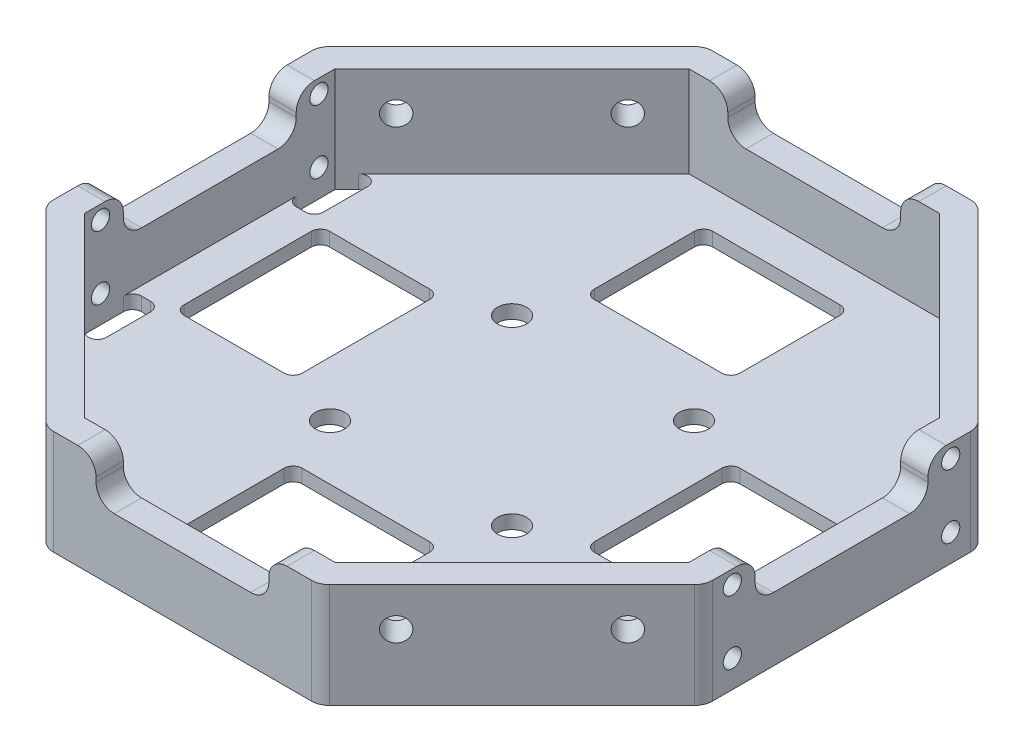
SolidWorks part; units mm, degrees
ref_plane "Front Plane" through (0, 0, 0) normal (0, 0, 1) x (1, 0, 0)
ref_plane "Top Plane" through (0, 0, 0) normal (0, 1, 0) x (1, 0, 0)
ref_plane "Right Plane" through (0, 0, 0) normal (1, 0, 0) x (0, 0, -1)
sketch "Sketch1" plane through (0, 0, 0) normal (0, 1, 0) x (1, 0, 0)
  line L1 (-11.2132, 40) -> (18.7868, 40)
  line L2 (18.7868, 40) -> (40, 18.7868)
  line L3 (40, 18.7868) -> (40, -11.2132)
  line L5 (-32.4264, 18.7868) -> (-32.4264, -11.2132)
  line L6 (-11.2132, 40) -> (-32.4264, 18.7868)
  line L7 (18.7868, -32.4264) -> (40, -11.2132)
  line L8 (-11.2132, -32.4264) -> (18.7868, -32.4264)
  line L9 (-11.2132, -32.4264) -> (-32.4264, -11.2132)
  point P13 (-32.4264, 3.7868)
  dimension "D1" = 30
  dimension "D2" = 30
  dimension "D3" = 40
  dimension "D4" = 40
extrude "Boss-Extrude1" add sketch "Sketch1" along normal blind 11.5
shell "Shell1" thickness 3 removed face at (3.7868, 11.5, -3.7868)
sketch "Sketch3" plane through (-21.8198, 0, 21.8198) normal (-0.7071, 0, 0.7071) x (0.7071, 0, 0.7071)
  line L0 (0, 11.5) -> (0, 7.25) construction
  line L1 (-15, 11.5) -> (15, 11.5) construction
  line L2 (0, 7.25) -> (9, 7.25) construction
  line L3 (0, 7.25) -> (-9, 7.25) construction
  circle A0 centre (-9, 7.25) radius 1.3
  circle A1 centre (9, 7.25) radius 1.3
extrude "Cut-Extrude1" cut sketch "Sketch3" against normal blind 94
sketch "Sketch4" plane through (-25.6066, 0, -25.6066) normal (-0.7071, 0, -0.7071) x (-0.7071, 0, 0.7071)
  line L0 (-5.3553, 11.5) -> (-5.3553, 7.25) construction
  line L1 (-20.3553, 11.5) -> (9.6447, 11.5) construction
  line L2 (-5.3553, 7.25) -> (-14.3553, 7.25) construction
  line L3 (-5.3553, 7.25) -> (3.6447, 7.25) construction
  circle A0 centre (-14.3553, 7.25) radius 1.3
  circle A1 centre (3.6447, 7.25) radius 1.3
extrude "Cut-Extrude2" cut sketch "Sketch4" against normal blind 94
fillet "Fillet1" radius 2 8 edges at (40, 5.75, 11.2132) (18.7868, 5.75, 32.4264) (40, 5.75, -18.7868) (18.7868, 5.75, -40) (-11.2132, 5.75, -40) (-32.4264, 5.75, -18.7868) (-32.4264, 5.75, 11.2132) (-11.2132, 5.75, 32.4264)
sketch "Sketch5" plane through (0, 0, 32.4264) normal (0, 0, 1) x (1, 0, 0)
  line L0 (3.7868, 11.5) -> (3.7868, 7) construction
  line L1 (-10.3848, 11.5) -> (17.9584, 11.5) construction
  line L2 (3.7868, 7) -> (13.2868, 7)
  line L3 (13.2868, 7) -> (13.2868, 11.5)
  line L4 (3.7868, 7) -> (-5.7132, 7)
  line L5 (-5.7132, 7) -> (-5.7132, 11.5)
  line L6 (-5.7132, 11.5) -> (13.2868, 11.5)
  dimension "D1" = 9.5
extrude "Cut-Extrude3" cut sketch "Sketch5" against normal blind 79
sketch "Sketch6" plane through (-32.4264, 0, 0) normal (-1, 0, 0) x (0, 0, 1)
  line L0 (-3.7868, 11.5) -> (-3.7868, 7) construction
  line L1 (-17.9584, 11.5) -> (10.3848, 11.5) construction
  line L2 (-3.7868, 7) -> (5.7132, 7)
  line L3 (5.7132, 7) -> (5.7132, 11.5)
  line L4 (-3.7868, 7) -> (-13.2868, 7)
  line L5 (-13.2868, 7) -> (-13.2868, 11.5)
  line L6 (-13.2868, 11.5) -> (5.7132, 11.5)
  dimension "D1" = 9.5
extrude "Cut-Extrude4" cut sketch "Sketch6" against normal blind 79
fillet "Fillet2" radius 2 16 edges at (38.5, 11.5, 5.7132) (38.5, 7, 5.7132) (38.5, 11.5, -13.2868) (38.5, 7, -13.2868) (13.2868, 11.5, 30.9264) (13.2868, 7, 30.9264) (-5.7132, 11.5, 30.9264) (-5.7132, 7, 30.9264) (-30.9264, 11.5, -13.2868) (-30.9264, 7, -13.2868) (-30.9264, 11.5, 5.7132) (-30.9264, 7, 5.7132) (13.2868, 11.5, -38.5) (13.2868, 7, -38.5) (-5.7132, 11.5, -38.5) (-5.7132, 7, -38.5)
sketch "Sketch7" plane through (0, 0, 0) normal (0, -1, 0) x (-1, 0, 0)
  circle A0 centre (6.2132, -6.2132) radius 1.6
  circle A1 centre (-13.7868, -6.2132) radius 1.6
  circle A2 centre (-13.7868, 13.7868) radius 1.6
  circle A3 centre (6.2132, 13.7868) radius 1.6
extrude "Cut-Extrude5" cut sketch "Sketch7" against normal blind 10
sketch "Sketch8" plane through (40, 0, 0) normal (1, 0, 0) x (0, 0, -1)
  line L0 (3.7868, 7) -> (-8.2132, 7) construction
  line L1 (11.2868, 7) -> (-3.7132, 7) construction
  line L2 (-8.2132, 7) -> (-8.2132, 10) construction
  line L3 (-8.2132, 7) -> (-8.2132, 3) construction
  line L4 (3.7868, 7) -> (3.7868, 3) construction
  line L5 (15.7868, 7) -> (15.7868, 3) construction
  circle A0 centre (-8.2132, 10) radius 1
  circle A1 centre (-8.2132, 3) radius 1
  circle A2 centre (15.7868, 3) radius 1
  circle A3 centre (15.7868, 10) radius 1
extrude "Cut-Extrude7" cut sketch "Sketch8" against normal blind 79
sketch "Sketch10" plane through (0, 3, 0) normal (0, 1, 0) x (1, 0, 0)
  line L0 (17.5442, 37) -> (37, 17.5442)
  line L1 (37, 17.5442) -> (37, -9.9706)
  line L2 (37, -9.9706) -> (17.5442, -29.4264)
  line L3 (17.5442, -29.4264) -> (-9.9706, -29.4264)
  line L4 (-9.9706, -29.4264) -> (-29.4264, -9.9706)
  line L5 (-29.4264, -9.9706) -> (-29.4264, 17.5442)
  line L6 (-29.4264, 17.5442) -> (-9.9706, 37)
  line L7 (-9.9706, 37) -> (17.5442, 37)
extrude "Cut-Extrude8" cut sketch "Sketch10" against normal blind 1.5
sketch "Sketch12" plane through (0, 1.5, 0) normal (0, 1, 0) x (1, 0, 0)
  line L0 (-29.4264, 17.5442) -> (-26.4264, 20.5442)
  line L1 (-29.4264, -3.7132) -> (-29.4264, 11.2868) construction
  line L2 (-29.4264, -5.7132) -> (-29.4264, -3.7132) construction
  line L3 (-29.4264, -4.7132) -> (-26.4264, -4.7132)
  line L4 (-26.4264, -4.7132) -> (-26.4264, -12.9706)
  line L5 (-29.4264, -9.9706) -> (-9.9706, -29.4264) construction
  line L6 (-29.4264, -4.7132) -> (-29.4264, -9.9706)
  line L7 (-29.4264, -9.9706) -> (-26.4264, -12.9706)
  line L8 (3.7868, 37) -> (3.7868, -29.4264)
  line L9 (-3.7132, 37) -> (11.2868, 37) construction
  line L10 (11.2868, -29.4264) -> (-3.7132, -29.4264) construction
  line L11 (-29.4264, 3.7868) -> (37, 3.7868)
  line L12 (37, 11.2868) -> (37, -3.7132) construction
  line L13 (-29.4264, 12.2868) -> (-29.4264, 17.5442)
  line L14 (-26.4264, 12.2868) -> (-26.4264, 20.5442)
  line L15 (-29.4264, 12.2868) -> (-26.4264, 12.2868)
  line L16 (37, -9.9706) -> (34, -12.9706)
  line L17 (37, -4.7132) -> (37, -9.9706)
  line L18 (34, -4.7132) -> (34, -12.9706)
  line L19 (37, -4.7132) -> (34, -4.7132)
  line L20 (37, 12.2868) -> (34, 12.2868)
  line L21 (34, 12.2868) -> (34, 20.5442)
  line L22 (37, 12.2868) -> (37, 17.5442)
  line L23 (37, 17.5442) -> (34, 20.5442)
  line M6 (-9.9706, 37) -> (-29.4264, 17.5442)
  line M7 (-29.4264, 17.5442) -> (-29.4264, -9.9706)
  line M8 (-29.4264, -9.9706) -> (-9.9706, -29.4264)
  line M10 (17.5442, -29.4264) -> (37, -9.9706)
  line M11 (37, -9.9706) -> (37, 17.5442)
  line M12 (37, 17.5442) -> (17.5442, 37)
extrude "Cut-Extrude9" cut sketch "Sketch12" against normal blind 1.5 contours L15 L14 M7 M6 | L4 L3 M7 M8 | L21 L20 M11 M12 | L19 L18 M11 M10 region at (35.389, 1.5, -15.721) region at (35.389, 1.5, 8.1474) region at (-27.8154, 1.5, 8.1474) region at (-27.8154, 1.5, -15.721)
fillet "Fillet3" radius 1 12 edges at (34, 0.75, -12.2868) (34, 0.75, -20.5442) (37, 0.75, -12.2868) (37, 0.75, 4.7132) (34, 0.75, 4.7132) (34, 0.75, 12.9706) (-26.4264, 0.75, 4.7132) (-26.4264, 0.75, 12.9706) (-29.4264, 0.75, 4.7132) (-26.4264, 0.75, -12.2868) (-29.4264, 0.75, -12.2868) (-26.4264, 0.75, -20.5442)
sketch "Sketch13" plane through (0, 1.5, 0) normal (0, 1, 0) x (1, 0, 0)
  line L2 (3.7868, 19.8383) -> (-4.2132, 19.8383)
  line L3 (-4.2132, 19.8383) -> (-4.2132, 32.8383)
  line L4 (-4.2132, 32.8383) -> (2.582, 32.8383)
  line L5 (3.7868, 19.8383) -> (11.7868, 19.8383)
  line L6 (11.7868, 19.8383) -> (11.7868, 32.8383)
  line L7 (11.7868, 32.8383) -> (2.582, 32.8383)
  line L11 (19.8383, 3.7868) -> (19.8383, -4.2132)
  line L12 (19.8383, -4.2132) -> (32.8383, -4.2132)
  line L13 (32.8383, -4.2132) -> (32.8383, 4.9916)
  line L14 (32.8383, 11.7868) -> (32.8383, 4.9916)
  line L15 (19.8383, 11.7868) -> (32.8383, 11.7868)
  line L16 (19.8383, 3.7868) -> (19.8383, 11.7868)
  line L17 (3.7868, -12.2647) -> (-4.2132, -12.2647)
  line L18 (-4.2132, -12.2647) -> (-4.2132, -25.2647)
  line L19 (-4.2132, -25.2647) -> (4.9916, -25.2647)
  line L20 (11.7868, -25.2647) -> (4.9916, -25.2647)
  line L21 (11.7868, -12.2647) -> (11.7868, -25.2647)
  line L22 (3.7868, -12.2647) -> (11.7868, -12.2647)
  line L23 (-12.2647, 3.7868) -> (-12.2647, 11.7868)
  line L24 (-12.2647, 11.7868) -> (-25.2647, 11.7868)
  line L25 (-25.2647, 11.7868) -> (-25.2647, 2.582)
  line L26 (-25.2647, -4.2132) -> (-25.2647, 2.582)
  line L27 (-12.2647, -4.2132) -> (-25.2647, -4.2132)
  line L28 (-12.2647, 3.7868) -> (-12.2647, -4.2132)
  dimension "D1" = 4
extrude "Cut-Extrude10" cut sketch "Sketch13" against normal blind 10
fillet "Fillet4" radius 1 16 edges at (11.7868, 0.75, 12.2647) (-4.2132, 0.75, 12.2647) (-4.2132, 0.75, 25.2647) (11.7868, 0.75, 25.2647) (32.8383, 0.75, 4.2132) (19.8383, 0.75, 4.2132) (19.8383, 0.75, -11.7868) (32.8383, 0.75, -11.7868) (11.7868, 0.75, -19.8383) (11.7868, 0.75, -32.8383) (-4.2132, 0.75, -19.8383) (-4.2132, 0.75, -32.8383) (-12.2647, 0.75, 4.2132) (-25.2647, 0.75, 4.2132) (-25.2647, 0.75, -11.7868) (-12.2647, 0.75, -11.7868)
